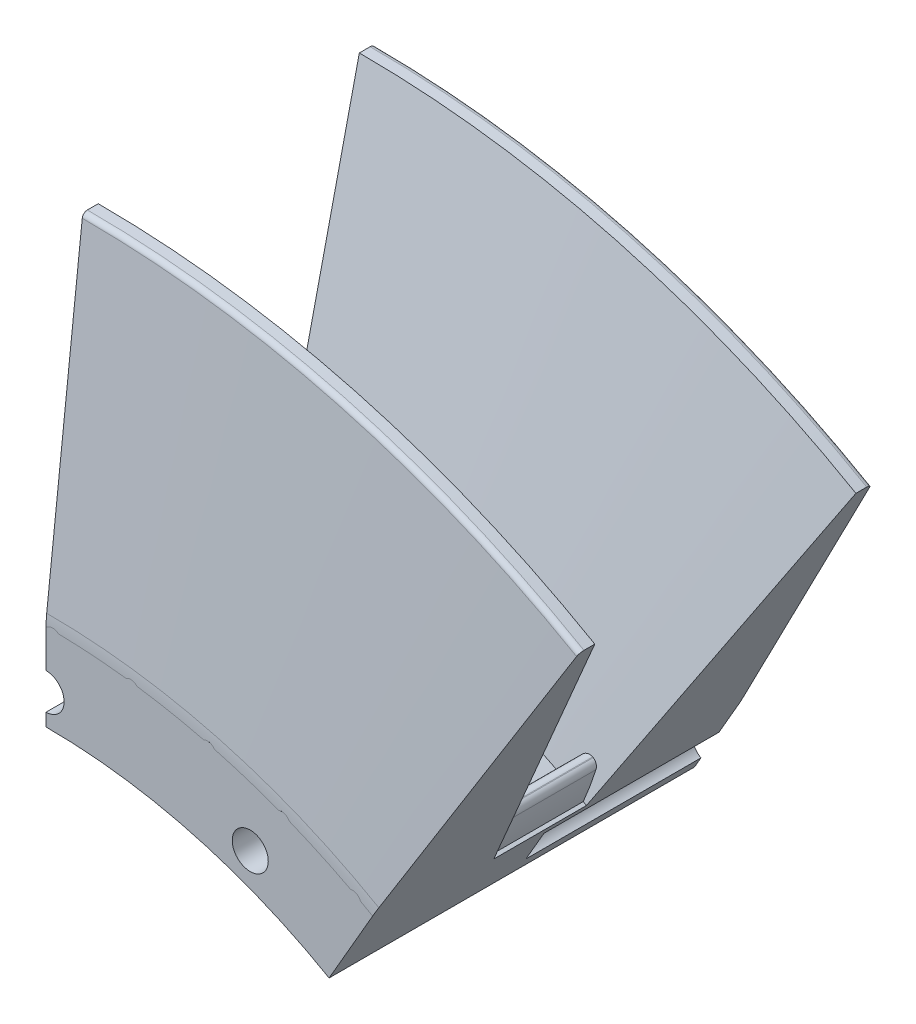
SolidWorks part; units mm, degrees
ref_plane "Alzado" through (0, 0, 0) normal (0, 0, 1) x (1, 0, 0)
ref_plane "Planta" through (0, 0, 0) normal (0, 1, 0) x (1, 0, 0)
ref_plane "Vista lateral" through (0, 0, 0) normal (1, 0, 0) x (0, 0, -1)
sketch "Croquis1" plane through (0, 0, 0) normal (0, 0, 1) x (1, 0, 0)
  line L0 (0, 0) -> (0, 63.65) construction
  line L1 (0, 63.3555) -> (20.3621, 55.9443)
  line L2 (0, 0) -> (0.7134, 68.5909) construction
  line L3 (1.3177, 63.3418) -> (-19.1941, 56.3558)
  circle A1 centre (0, 0) radius 60.5 construction
  circle A2 centre (0, 0) radius 59.5347 construction
  circle A3 centre (0, 0) radius 63.3555 construction
  circle A4 centre (0, 0) radius 63.65 construction
  arc A5 (0.1096, 63.6499) -> (-0.8237, 60.4944) centre (20.3621, 55.9443) ccw
  arc A6 (1.2143, 63.6384) -> (2.0817, 60.4642) centre (-19.1941, 56.3558) cw
  arc A7 (-0.8237, 60.4944) -> (2.0817, 60.4642) centre (0, 0) cw
  arc A8 (0.1096, 63.6499) -> (1.2143, 63.6384) centre (0, 0) cw
  dimension "df" = 121
  dimension "db" = 119.0695
  dimension "dp" = 126.7111
  dimension "de" = 127.3
  dimension "angulo_paso" = 20
  dimension "s" = 1.3178
sketch "Croquis2" plane through (0, 0, 0) normal (0, 0, 1) x (1, 0, 0)
  circle A0 centre (0, 0) radius 60.5 construction
  circle A1 centre (0, 0) radius 63.65 construction
  arc A2 (2.0817, 60.4642) -> (1.2143, 63.6384) centre (-19.1941, 56.3558) ccw construction
  arc A3 (0.1096, 63.6499) -> (-0.8237, 60.4944) centre (20.3621, 55.9443) ccw construction
  arc A4 (-0.8237, 60.4944) -> (2.0817, 60.4642) centre (0, 0) ccw
  arc A5 (1.2143, 63.6384) -> (0.1096, 63.6499) centre (0, 0) ccw
  arc A6 (2.0817, 60.4642) -> (1.2143, 63.6384) centre (-19.1941, 56.3558) ccw
  arc A7 (0.1096, 63.6499) -> (-0.8237, 60.4944) centre (20.3621, 55.9443) ccw
  circle A8 centre (0, 0) radius 55
  dimension "D1" = 110
extrude "Saliente-Extruir1" add sketch "Croquis2" along normal mid plane 35.5
fillet "Redondeo1" radius 0.7341 2 edges at (0.1096, 63.6499, 0) (1.2143, 63.6384, 0)
pattern_circular "MatrizC1" count 52 over 360 about axis through (0, 0, 17.75) along (0, 0, 1) of "Saliente-Extruir1", "Redondeo1"
sketch "Croquis3" plane through (0, 0, 0) normal (1, 0, 0) x (0, 0, -1)
  line L0 (0, 114.3236) -> (0, -114.3236) construction
  line L1 (-93.0613, 0) -> (93.0613, 0) construction
  line L2 (17.75, 55) -> (-17.75, 55)
  line L3 (-17.75, 55) -> (-17.75, 63.4532)
  line L4 (-14.2339, 96.0545) -> (-17.6904, 64.5436)
  line L5 (4.5, 60.5) -> (-4.5, 60.5)
  line L6 (-4.5, 60.5) -> (-12.685, 96.5)
  line L7 (-12.685, 96.5) -> (-13.7368, 96.5)
  line L8 (-19.75, 66) -> (-22.75, 66) construction
  line L9 (19.75, 66) -> (22.75, 66) construction
  line L10 (12.685, 96.5) -> (13.7368, 96.5)
  line L11 (4.5, 60.5) -> (12.685, 96.5)
  line L12 (14.2339, 96.0545) -> (17.6904, 64.5436)
  line L13 (17.75, 55) -> (17.75, 63.4532)
  arc A0 (-17.75, 64) -> (-19.75, 66) centre (-19.75, 64) ccw construction
  arc A1 (-17.75, 63.4532) -> (-17.6904, 64.5436) centre (-7.75, 63.4532) cw
  arc A2 (-14.2339, 96.0545) -> (-13.7368, 96.5) centre (-13.7368, 96) cw
  arc A3 (17.75, 64) -> (19.75, 66) centre (19.75, 64) cw construction
  arc A4 (14.2339, 96.0545) -> (13.7368, 96.5) centre (13.7368, 96) ccw
  arc A5 (17.75, 63.4532) -> (17.6904, 64.5436) centre (7.75, 63.4532) ccw
  point P0 (14.185, 96.5)
  point P4 (0, 0)
  point P8 (0, 0)
  point P16 (-17.75, 66)
  point P23 (-14.185, 96.5)
  point P36 (0, 60.5)
  point P37 (0, 55)
  point P38 (17.75, 66)
  dimension "D9" = 2
  dimension "D11" = 10
  dimension "D12" = 0.5
  dimension "D1" = 110
  dimension "D2" = 35.5
  dimension "D3" = 9
  dimension "D4" = 121
  dimension "D5" = 25.37
  dimension "D6" = 36
  dimension "D7" = 11
  dimension "D8" = 5
  dimension "D10" = 1.5
revolve "Revolución1" add sketch "Croquis3" angle 30 about L1
sketch "Croquis4" plane through (0, 0, 0) normal (0, 0, 1) x (1, 0, 0)
  circle A0 centre (0, 58) radius 1.75
  circle A1 centre (0, 0) radius 58 construction
  circle A2 centre (19.8372, 54.5022) radius 1.75
  circle A3 centre (37.2817, 44.4306) radius 1.75
  circle A4 centre (50.2295, 29) radius 1.75
  circle A5 centre (57.1188, 10.0716) radius 1.75
  circle A6 centre (57.1188, -10.0716) radius 1.75
  circle A7 centre (50.2295, -29) radius 1.75
  circle A8 centre (37.2817, -44.4306) radius 1.75
  circle A9 centre (19.8372, -54.5022) radius 1.75
  circle A10 centre (0, -58) radius 1.75
  circle A11 centre (-19.8372, -54.5022) radius 1.75
  circle A12 centre (-37.2817, -44.4306) radius 1.75
  circle A13 centre (-50.2295, -29) radius 1.75
  circle A14 centre (-57.1188, -10.0716) radius 1.75
  circle A15 centre (-57.1188, 10.0716) radius 1.75
  circle A16 centre (-50.2295, 29) radius 1.75
  circle A17 centre (-37.2817, 44.4306) radius 1.75
  circle A18 centre (-19.8372, 54.5022) radius 1.75
  point P43 (0, 0)
  dimension "D2" = 3.5
  dimension "D1" = 58
  dimension "D3" = 18
extrude "Cortar-Extruir1" cut sketch "Croquis4" against normal blind 17 from surface starting at face at (-0.2825, -0.705, 17.75)
sketch "Croquis5" plane through (0, 0, 0) normal (0, 0, 1) x (1, 0, 0)
  circle A0 centre (0, 0) radius 58 construction
  circle A1 centre (0, 0) radius 58 construction
  arc A2 (0, 58) -> (19.8372, 54.5022) centre (0, 0) cw construction
  circle A3 centre (10.0716, 57.1188) radius 1.75
  circle A4 centre (19.8372, 54.5022) radius 1.75 construction
  circle A5 centre (29, 50.2295) radius 1.75
  circle A6 centre (44.4306, 37.2817) radius 1.75
  circle A7 centre (54.5022, 19.8372) radius 1.75
  circle A8 centre (58, 0) radius 1.75
  circle A9 centre (54.5022, -19.8372) radius 1.75
  circle A10 centre (44.4306, -37.2817) radius 1.75
  circle A11 centre (29, -50.2295) radius 1.75
  circle A12 centre (10.0716, -57.1188) radius 1.75
  circle A13 centre (-10.0716, -57.1188) radius 1.75
  circle A14 centre (-29, -50.2295) radius 1.75
  circle A15 centre (-44.4306, -37.2817) radius 1.75
  circle A16 centre (-54.5022, -19.8372) radius 1.75
  circle A17 centre (-58, 0) radius 1.75
  circle A18 centre (-54.5022, 19.8372) radius 1.75
  circle A19 centre (-44.4306, 37.2817) radius 1.75
  circle A20 centre (-29, 50.2295) radius 1.75
  circle A21 centre (-10.0716, 57.1188) radius 1.75
  point P48 (0, 0)
  dimension "D1" = 18
extrude "Cortar-Extruir2" cut sketch "Croquis5" along normal blind 17 from surface starting at face at (55, 0, -17.75)
sketch "Croquis6" plane through (0, 0, 0) normal (0, 0, 1) x (1, 0, 0)
  line L0 (0, 96.0545) -> (0, 0)
  line L1 (0, 0) -> (48.0273, 83.1857)
  arc A0 (0, 96.0545) -> (48.0273, 83.1857) centre (0, 0) ccw
extrude "Cortar-Extruir4" cut sketch "Croquis6" along normal through all both and the other way through all contours A0 L1 L0
equation "\"m\"= 2.4469"
equation "\"ϕ\"= 20"
equation "\"dp@Croquis1\" = \"df@Croquis1\" +  ( \"m\" * 2.334 ) "
equation "\"db@Croquis1\" = \"dp@Croquis1\" * cos ( \"ϕ\" ) "
equation "\"Z\"= \"dp@Croquis1\" / \"m\""
equation "\"s@Croquis1\"= \"m\" * ( 1.2 / 7 ) * 3.1415926535897932384626433832795"
equation "\"D1@Redondeo1\"=\"m\"*0.3"
equation "\"D1@MatrizC1\"=\"Z\""
